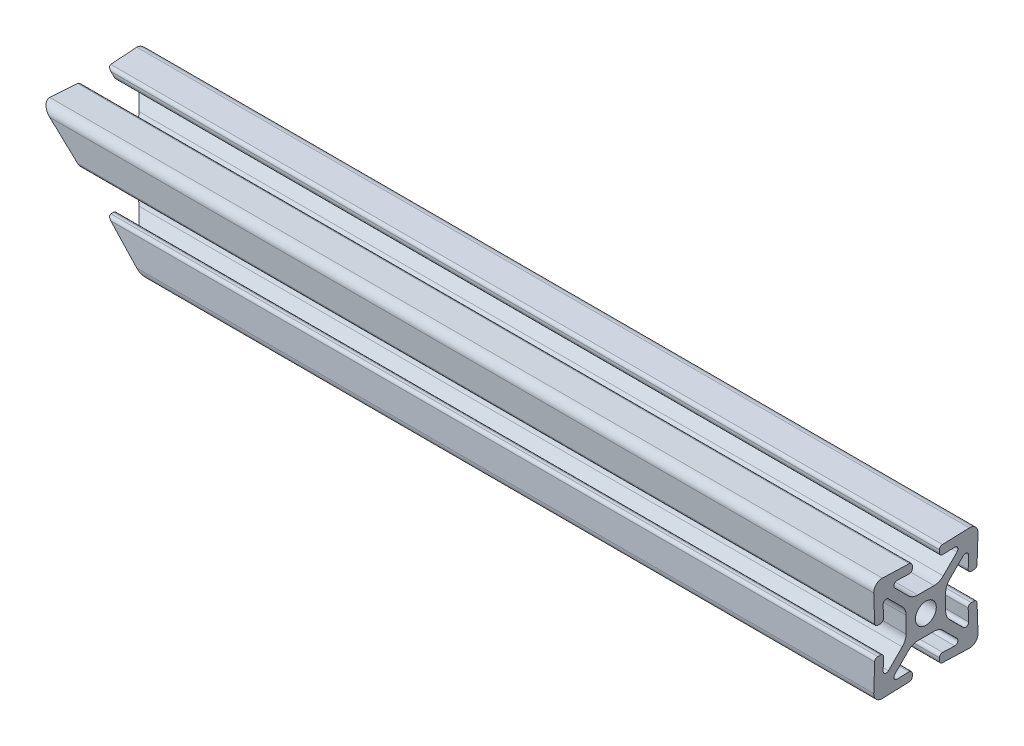
SolidWorks part; units mm, degrees
ref_plane "Front Plane" through (0, 0, 0) normal (0, 0, 1) x (1, 0, 0)
ref_plane "Top Plane" through (0, 0, 0) normal (0, 1, 0) x (1, 0, 0)
ref_plane "Right Plane" through (0, 0, 0) normal (1, 0, 0) x (0, 0, -1)
sketch "Sketch1" plane through (0, 0, 0) normal (1, 0, 0) x (0, 0, -1)
  line L0 (0, -12.7) -> (0, 12.7) construction
  line L1 (-7.874, 12.7) -> (7.874, 12.7) construction
  line L2 (-12.7, 0) -> (12.7, 0) construction
  line L3 (-7.874, 12.7) -> (-7.874, 4.826) construction
  line L4 (-3.302, 12.7) -> (3.302, 12.7) construction
  line L5 (-12.7, -12.7) -> (12.7, -12.7) construction
  line L6 (-12.7, 12.7) -> (12.7, 12.7) construction
  circle A0 centre (0, 0) radius 2.54 construction
  point P7 (0, 12.7)
  point P10 (0, 0)
  point P13 (0, 0)
  point P16 (0, 12.7)
  point P17 (-3.302, 12.7)
  point P18 (3.302, 12.7)
  point P21 (0, -12.7)
  point P24 (0, 12.7)
  dimension "Center Hole Diameter" = 5.08
  dimension "Rail Width" = 25.4
  dimension "Rail Height" = 25.4
  dimension "T-Slot Depth" = 7.874
  dimension "D1" = 15.748
  dimension "T-Slot Width" = 6.604
  dimension "D2" = 12.7
sketch "Sketch2" plane through (0, 0, 0) normal (0, 0, 1) x (1, 0, 0)
  line L0 (-101.4131, 0) -> (101.4131, 0) construction
  line L1 (0, 0) -> (0, 26.104) construction
  line L2 (101.4131, -12.7) -> (101.4131, 12.7) construction
  line L3 (-101.4131, -12.7) -> (-101.4131, 12.7) construction
  point P3 (-63.3131, 0)
  point P8 (0, 0)
  point P9 (63.3131, 0)
  point P12 (101.4131, 0)
  point P15 (-101.4131, 0)
  dimension "Length" = 202.8261
  dimension "D1" = 38.1
  dimension "D2" = 25.4
sketch "Sketch3" plane through (0, 0, 0) normal (1, 0, 0) x (0, 0, -1)
  line L0 (0, 4.826) -> (1.9842, 4.826)
  line L1 (0, -12.7) -> (0, 12.7) construction
  line L2 (4.2293, 5.7559) -> (7.5866, 9.1132)
  line L6 (7.0212, 10.4136) -> (4.0906, 10.3112)
  line L7 (3.302, 11.0728) -> (3.302, 11.7082)
  line L8 (-7.874, 12.7) -> (7.874, 12.7) construction
  line L10 (0, 0) -> (12.7, 12.7) construction
  line L13 (0, 4.826) -> (0, 2.54)
  line L14 (4.826, 0) -> (2.54, 0)
  line L31 (4.826, 0) -> (4.826, 1.9842)
  line L32 (4.0374, 12.4697) -> (10.5971, 12.6988)
  line L33 (-12.7, 0) -> (12.7, 0) construction
  line L34 (-12.7, 12.7) -> (12.7, 12.7) construction
  line L35 (5.7559, 4.2293) -> (9.1132, 7.5866)
  line L36 (0, 12.7) -> (12.7, 12.7) construction
  line L37 (12.7, 12.7) -> (12.7, 8.0234) construction
  line L38 (11.0728, 3.302) -> (11.7082, 3.302)
  line L39 (10.4136, 7.0212) -> (10.3112, 4.0906)
  line L40 (12.6988, 10.5971) -> (12.4697, 4.0374)
  arc A0 (2.54, 0) -> (0, 2.54) centre (0, 0) ccw
  arc A1 (1.9842, 4.826) -> (4.2293, 5.7559) centre (1.9842, 8.001) ccw
  circle A2 centre (0, 0) radius 2.54 construction
  arc A7 (3.302, 11.7082) -> (4.0374, 12.4697) centre (4.064, 11.7082) cw
  arc A8 (4.0906, 10.3112) -> (3.302, 11.0728) centre (4.064, 11.0728) cw
  arc A14 (4.826, 1.9842) -> (5.7559, 4.2293) centre (8.001, 1.9842) cw
  arc A16 (10.5971, 12.6988) -> (12.6988, 10.5971) centre (10.668, 10.668) cw
  arc A17 (7.0212, 10.4136) -> (7.5866, 9.1132) centre (7.0478, 9.652) cw
  arc A18 (10.4136, 7.0212) -> (9.1132, 7.5866) centre (9.652, 7.0478) ccw
  arc A19 (10.3112, 4.0906) -> (11.0728, 3.302) centre (11.0728, 4.064) ccw
  arc A20 (11.7082, 3.302) -> (12.4697, 4.0374) centre (11.7082, 4.064) ccw
  point P37 (3.2994, 4.826)
  point P49 (12.7, 3.302)
  point P52 (3.302, 12.7)
  point P55 (3.302, 10.2837)
  dimension "D4" = 3.175
  dimension "D9" = 2.159
  dimension "D12" = 0.762
  dimension "D3" = 2.032
  dimension "D8" = 0.762
  dimension "D2" = 45
  dimension "D5" = 2
  dimension "D6" = 45
  dimension "D7" = 2.159
extrude "Boss-Extrude1" add sketch "Sketch3" against normal up to vertex (101.4131 mm away) and the other way up to vertex (101.4131 mm away) up to point (-101.4131, 0, 0) other way up to point (101.4131, 0, 0)
mirror "Mirror1" about plane through (0, 0, 0) normal (0, 1, 0) of bodies 104
mirror "Mirror2" about plane through (0, 0, 0) normal (0, 0, 1) of bodies 105
ref_plane "Plane1" through (0, 0, 12.6988) normal (0, 0, -1) x (-1, 0, 0)
sketch "Sketch7" plane through (-101.4131, 0, 0) normal (-1, 0, 0) x (0, 0, 1)
  line L0 (10.5971, 12.6988) -> (12.6988, 10.5971)
  line L1 (12.6988, 10.5971) -> (12.6988, 12.6988)
  line L2 (12.6988, 12.6988) -> (10.5971, 12.6988)
  line L3 (10.5971, -12.6988) -> (12.6988, -10.5971)
  line L4 (12.6988, -10.5971) -> (12.6988, -12.6988)
  line L5 (12.6988, -12.6988) -> (10.5971, -12.6988)
ref_plane "Plane3" through (0, 0, 38.1) normal (0, 0, 1) x (1, 0, 0)
sketch "Sketch10" plane through (0, 0, 38.1) normal (0, 0, 1) x (1, 0, 0)
  line L0 (-101.4131, -12.7) -> (-76.0131, -12.7)
  line L1 (-101.4131, -12.7) -> (101.4131, -12.7) construction
  line L2 (-76.0131, -12.7) -> (-101.4131, 12.7)
  line L3 (-101.4131, 12.7) -> (-101.4131, -12.7)
  line L4 (-101.4131, 12.7) -> (-72.5452, -16.1679)
  line L5 (-72.5452, -16.1679) -> (-105.9605, -16.1679)
  line L6 (-72.5452, -16.1679) -> (-106.4546, 17.7415)
  line L7 (-106.4546, 17.7415) -> (-105.9605, -16.1679)
  dimension "D1" = 45
extrude "Cut-Extrude7" cut sketch "Sketch10" against normal through all contours L2 L3 L0 | L6 L7 L5 L4 L0 L3 region at (-92.9464, -4.2333, 38.1) region at (-88.7131, -13.1796, 38.1)
equation "\"D1@Sketch2\"=\"Rail Height@Sketch1\"*1.5"
equation "\"D2@Sketch2\"=\"Rail Height@Sketch1\""
